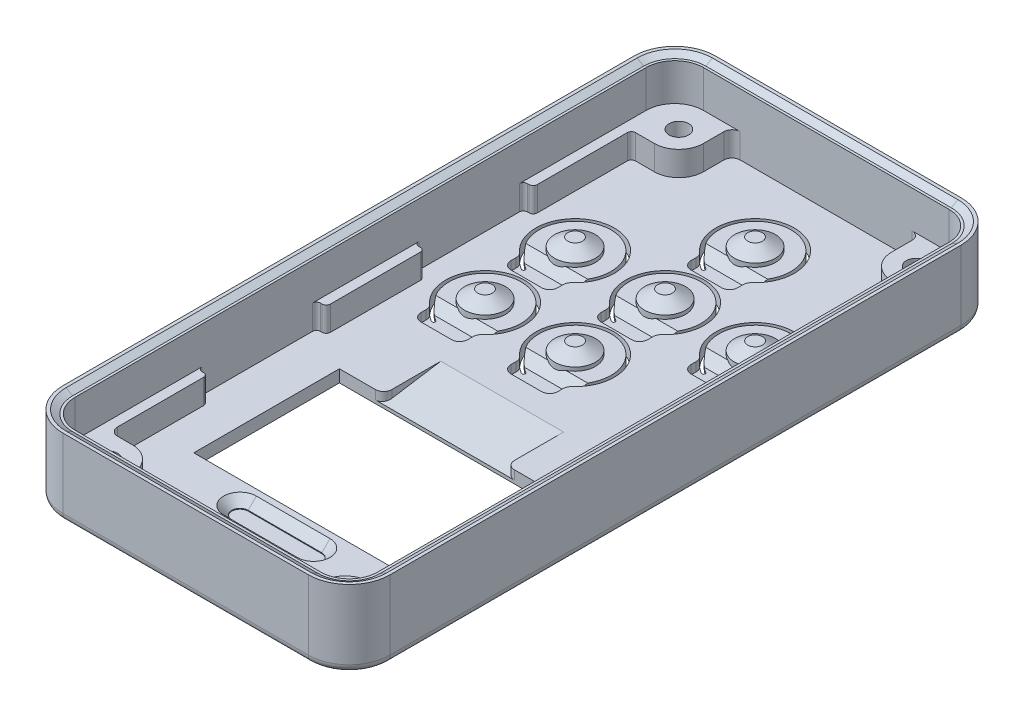
SolidWorks part; units mm, degrees
ref_plane "Front Plane" through (0, 0, 0) normal (0, 0, 1) x (1, 0, 0)
ref_plane "Top Plane" through (0, 0, 0) normal (0, 1, 0) x (1, 0, 0)
ref_plane "Right Plane" through (0, 0, 0) normal (1, 0, 0) x (0, 0, -1)
sketch "Base Sketch" plane through (0, 0, 0) normal (0, 1, 0) x (1, 0, 0)
  line L0 (0, 0) -> (40, 0)
  line L1 (40, 0) -> (40, 79.79)
  line L2 (40, 79.79) -> (0, 79.79)
  line L3 (0, 79.79) -> (0, 0)
extrude "Base" add sketch "Base Sketch" along normal blind 9.5
fillet "Corner Rounds R5" radius 5 4 edges at (0, 4.75, -79.79) (40, 4.75, -79.79) (40, 4.75, 0) (0, 4.75, 0)
shell "Shell 1.5" thickness 1.5 removed face at (20, 9.5, -39.895)
sketch "Boss Sketch" plane through (0, 0, 0) normal (0, 1, 0) x (1, 0, 0)
  line L0 (1.5, 1.5) -> (8.5, 1.5)
  line L1 (8.5, 1.5) -> (8.5, 5)
  line L2 (5.5, 8) -> (1.5, 8)
  line L3 (1.5, 8) -> (1.5, 1.5)
  line L4 (38.5, 1.5) -> (31.5, 1.5)
  line L5 (31.5, 1.5) -> (31.5, 5)
  line L6 (34.5, 8) -> (38.5, 8)
  line L7 (38.5, 8) -> (38.5, 1.5)
  line L16 (1.5, 78.29) -> (8.5, 78.29)
  line L17 (8.5, 78.29) -> (8.5, 74.79)
  line L18 (5.5, 71.79) -> (1.5, 71.79)
  line L19 (1.5, 71.79) -> (1.5, 78.29)
  line L20 (38.5, 78.29) -> (31.5, 78.29)
  line L21 (31.5, 78.29) -> (31.5, 74.79)
  line L22 (34.5, 71.79) -> (38.5, 71.79)
  line L23 (38.5, 71.79) -> (38.5, 78.29)
  arc A0 (8.5, 5) -> (5.5, 8) centre (5.4999, 4.9999) ccw
  circle A1 centre (5.5, 5) radius 1
  arc A2 (31.5, 5) -> (34.5, 8) centre (34.5001, 4.9999) cw
  circle A3 centre (34.5, 5) radius 1
  circle A5 centre (5.5, 74.79) radius 1
  circle A7 centre (34.5, 74.79) radius 1
  arc A8 (8.5, 74.79) -> (5.5, 71.79) centre (5.4999, 74.7901) cw
  arc A9 (31.5, 74.79) -> (34.5, 71.79) centre (34.5001, 74.7901) ccw
extrude "Corner Bosses (stop at ledge y4.5) + M2 Holes" add sketch "Boss Sketch" along normal blind 4.5
sketch "Ledge Sketch" plane through (0, 0, 0) normal (0, 1, 0) x (1, 0, 0)
  line L0 (1.5, 8) -> (2.7, 8)
  line L1 (2.7, 8) -> (2.7, 20)
  line L2 (2.7, 20) -> (1.5, 20)
  line L3 (1.5, 20) -> (1.5, 8)
  line L4 (37.3, 8) -> (38.5, 8)
  line L5 (38.5, 8) -> (38.5, 20)
  line L6 (38.5, 20) -> (37.3, 20)
  line L7 (37.3, 20) -> (37.3, 8)
  line L8 (1.5, 34.5) -> (2.7, 34.5)
  line L9 (2.7, 34.5) -> (2.7, 46.5)
  line L10 (2.7, 46.5) -> (1.5, 46.5)
  line L11 (1.5, 46.5) -> (1.5, 34.5)
  line L12 (37.3, 34.5) -> (38.5, 34.5)
  line L13 (38.5, 34.5) -> (38.5, 46.5)
  line L14 (38.5, 46.5) -> (37.3, 46.5)
  line L15 (37.3, 46.5) -> (37.3, 34.5)
  line L16 (1.5, 59.79) -> (2.7, 59.79)
  line L17 (2.7, 59.79) -> (2.7, 71.79)
  line L18 (2.7, 71.79) -> (1.5, 71.79)
  line L19 (1.5, 71.79) -> (1.5, 59.79)
  line L20 (37.3, 59.79) -> (38.5, 59.79)
  line L21 (38.5, 59.79) -> (38.5, 71.79)
  line L22 (38.5, 71.79) -> (37.3, 71.79)
  line L23 (37.3, 71.79) -> (37.3, 59.79)
extrude "Side Ledges" add sketch "Ledge Sketch" along normal blind 4.5
fillet "Outer Face Round R1" radius 1 8 edges at (1.4645, 0, -1.4645) (20, 0, 0) (38.5355, 0, -1.4645) (40, 0, -39.895) (38.5355, 0, -78.3255) (20, 0, -79.79) (1.4645, 0, -78.3255) (0, 0, -39.895)
sketch "Window Sketch" plane through (0, 0, 0) normal (0, 1, 0) x (1, 0, 0)
  line L0 (7.1, 14.5) -> (32.9, 14.5)
  line L1 (32.9, 14.5) -> (32.9, 31.7)
  line L2 (32.9, 31.7) -> (7.1, 31.7)
  line L3 (7.1, 31.7) -> (7.1, 14.5)
extrude "Display Window" cut sketch "Window Sketch" along normal through all
ref_plane "Mid Plane X20" through (20, 0, 0) normal (1, 0, 0) x (0, 0, -1)
sketch "Ramp Sketch" plane through (20, 0, 0) normal (1, 0, 0) x (0, 0, -1)
  line L0 (31, 0.4) -> (31.7, 0.4)
  line L1 (31.7, 0.4) -> (38.7, 1.5)
  line L2 (38.7, 1.5) -> (38.7, 2.5)
  line L3 (38.7, 2.5) -> (31, 2.5)
  line L4 (31, 2.5) -> (31, 0.4)
extrude "Cable Ramp" cut sketch "Ramp Sketch" against normal blind 7.5 and the other way blind 7.5
ref_plane "Plate Inner Face" through (0, 1.5, 0) normal (0, 1, 0) x (1, 0, 0)
sketch "LED Window Sketch" plane through (0, 1.5, 0) normal (0, 1, 0) x (1, 0, 0)
  circle A0 centre (20, 7.28) radius 1.7
  dimension "D1" = 3.4
extrude "LED Window" cut sketch "LED Window Sketch" against normal blind 1.1
sketch "Plunger Stems Sketch" plane through (0, 1.5, 0) normal (0, 1, 0) x (1, 0, 0)
  circle A0 centre (9, 47.6) radius 2.5
  circle A1 centre (20, 47.6) radius 2.5
  circle A2 centre (9, 58.6) radius 2.5
  circle A3 centre (20, 58.6) radius 2.5
  circle A4 centre (31, 58.6) radius 2.5
  circle A5 centre (20, 69.6) radius 2.5
extrude "Plunger Stems 5.0" add sketch "Plunger Stems Sketch" along normal blind 0.45
ref_plane "Plunger Cone Base" through (0, 1.95, 0) normal (0, 1, 0) x (1, 0, 0)
sketch "Plunger Cone Sketch" plane through (0, 1.95, 0) normal (0, 1, 0) x (1, 0, 0)
  circle A0 centre (9, 47.6) radius 2.5
  circle A1 centre (20, 47.6) radius 2.5
  circle A2 centre (9, 58.6) radius 2.5
  circle A3 centre (20, 58.6) radius 2.5
  circle A4 centre (31, 58.6) radius 2.5
  circle A5 centre (20, 69.6) radius 2.5
extrude "Plunger Cones to 1.8" add sketch "Plunger Cone Sketch" along normal blind 1 draft 57.995
fillet "Boss Junction Fillets R1" radius 1 7 edges at (37.3, 3, -71.79) (37.3, 3, -8) (2.7, 3, -8) (31.5, 3, -78.29) (8.5, 3, -78.29) (31.5, 3, -1.5) (8.5, 3, -1.5)
sketch "C-Slot Sketch" plane through (0, 0, 0) normal (0, 1, 0) x (1, 0, 0)
  arc A0 (10.4434, 43.0222) -> (7.5566, 43.0222) centre (9, 47.6) ccw
  arc A1 (7.5566, 43.0222) -> (7.6769, 43.4036) centre (7.6168, 43.2129) ccw
  arc A2 (7.6769, 43.4036) -> (10.3231, 43.4036) centre (9, 47.6) cw
  arc A3 (10.3231, 43.4036) -> (10.4434, 43.0222) centre (10.3832, 43.2129) ccw
  arc A4 (21.4434, 43.0222) -> (18.5566, 43.0222) centre (20, 47.6) ccw
  arc A5 (18.5566, 43.0222) -> (18.6769, 43.4036) centre (18.6168, 43.2129) ccw
  arc A6 (18.6769, 43.4036) -> (21.3231, 43.4036) centre (20, 47.6) cw
  arc A7 (21.3231, 43.4036) -> (21.4434, 43.0222) centre (21.3832, 43.2129) ccw
  arc A8 (10.4434, 54.0222) -> (7.5566, 54.0222) centre (9, 58.6) ccw
  arc A9 (7.5566, 54.0222) -> (7.6769, 54.4036) centre (7.6168, 54.2129) ccw
  arc A10 (7.6769, 54.4036) -> (10.3231, 54.4036) centre (9, 58.6) cw
  arc A11 (10.3231, 54.4036) -> (10.4434, 54.0222) centre (10.3832, 54.2129) ccw
  arc A12 (21.4434, 54.0222) -> (18.5566, 54.0222) centre (20, 58.6) ccw
  arc A13 (18.5566, 54.0222) -> (18.6769, 54.4036) centre (18.6168, 54.2129) ccw
  arc A14 (18.6769, 54.4036) -> (21.3231, 54.4036) centre (20, 58.6) cw
  arc A15 (21.3231, 54.4036) -> (21.4434, 54.0222) centre (21.3832, 54.2129) ccw
  arc A16 (32.4434, 54.0222) -> (29.5566, 54.0222) centre (31, 58.6) ccw
  arc A17 (29.5566, 54.0222) -> (29.6769, 54.4036) centre (29.6168, 54.2129) ccw
  arc A18 (29.6769, 54.4036) -> (32.3231, 54.4036) centre (31, 58.6) cw
  arc A19 (32.3231, 54.4036) -> (32.4434, 54.0222) centre (32.3832, 54.2129) ccw
  arc A20 (21.4434, 65.0222) -> (18.5566, 65.0222) centre (20, 69.6) ccw
  arc A21 (18.5566, 65.0222) -> (18.6769, 65.4036) centre (18.6168, 65.2129) ccw
  arc A22 (18.6769, 65.4036) -> (21.3231, 65.4036) centre (20, 69.6) cw
  arc A23 (21.3231, 65.4036) -> (21.4434, 65.0222) centre (21.3832, 65.2129) ccw
sketch "Sketch10" plane through (0, 1.5, 0) normal (0, 1, 0) x (1, 0, 0)
  line L0 (11.864, 44.259) -> (11.864, 41.636)
  line L1 (11.864, 41.636) -> (6.136, 41.636)
  line L2 (6.136, 41.636) -> (6.136, 44.259)
  line L3 (6.136, 44.259) -> (11.864, 44.259)
  line L4 (22.864, 44.259) -> (22.864, 41.636)
  line L5 (22.864, 41.636) -> (17.136, 41.636)
  line L6 (17.136, 41.636) -> (17.136, 44.259)
  line L7 (17.136, 44.259) -> (22.864, 44.259)
  line L8 (11.864, 55.259) -> (11.864, 52.636)
  line L9 (11.864, 52.636) -> (6.136, 52.636)
  line L10 (6.136, 52.636) -> (6.136, 55.259)
  line L11 (6.136, 55.259) -> (11.864, 55.259)
  line L12 (22.864, 55.259) -> (22.864, 52.636)
  line L13 (22.864, 52.636) -> (17.136, 52.636)
  line L14 (17.136, 52.636) -> (17.136, 55.259)
  line L15 (17.136, 55.259) -> (22.864, 55.259)
  line L16 (33.864, 55.259) -> (33.864, 52.636)
  line L17 (33.864, 52.636) -> (28.136, 52.636)
  line L18 (28.136, 52.636) -> (28.136, 55.259)
  line L19 (28.136, 55.259) -> (33.864, 55.259)
  line L20 (22.864, 66.259) -> (22.864, 63.636)
  line L21 (22.864, 63.636) -> (17.136, 63.636)
  line L22 (17.136, 63.636) -> (17.136, 66.259)
  line L23 (17.136, 66.259) -> (22.864, 66.259)
extrude "Cut-Extrude7" cut sketch "Sketch10" against normal blind 1.1
sketch "Sketch11" plane through (0, 0, 0) normal (0, 1, 0) x (1, 0, 0)
  arc A0 (11.4, 43.4431) -> (6.6, 43.4431) centre (9, 47.6) ccw
  arc A1 (6.6, 43.4431) -> (6.8, 43.7895) centre (6.7, 43.6163) ccw
  arc A2 (6.8, 43.7895) -> (11.2, 43.7895) centre (9, 47.6) cw
  arc A3 (11.2, 43.7895) -> (11.4, 43.4431) centre (11.3, 43.6163) ccw
  arc A4 (22.4, 43.4431) -> (17.6, 43.4431) centre (20, 47.6) ccw
  arc A5 (17.6, 43.4431) -> (17.8, 43.7895) centre (17.7, 43.6163) ccw
  arc A6 (17.8, 43.7895) -> (22.2, 43.7895) centre (20, 47.6) cw
  arc A7 (22.2, 43.7895) -> (22.4, 43.4431) centre (22.3, 43.6163) ccw
  arc A8 (11.4, 54.4431) -> (6.6, 54.4431) centre (9, 58.6) ccw
  arc A9 (6.6, 54.4431) -> (6.8, 54.7895) centre (6.7, 54.6163) ccw
  arc A10 (6.8, 54.7895) -> (11.2, 54.7895) centre (9, 58.6) cw
  arc A11 (11.2, 54.7895) -> (11.4, 54.4431) centre (11.3, 54.6163) ccw
  arc A12 (22.4, 54.4431) -> (17.6, 54.4431) centre (20, 58.6) ccw
  arc A13 (17.6, 54.4431) -> (17.8, 54.7895) centre (17.7, 54.6163) ccw
  arc A14 (17.8, 54.7895) -> (22.2, 54.7895) centre (20, 58.6) cw
  arc A15 (22.2, 54.7895) -> (22.4, 54.4431) centre (22.3, 54.6163) ccw
  arc A16 (33.4, 54.4431) -> (28.6, 54.4431) centre (31, 58.6) ccw
  arc A17 (28.6, 54.4431) -> (28.8, 54.7895) centre (28.7, 54.6163) ccw
  arc A18 (28.8, 54.7895) -> (33.2, 54.7895) centre (31, 58.6) cw
  arc A19 (33.2, 54.7895) -> (33.4, 54.4431) centre (33.3, 54.6163) ccw
  arc A20 (22.4, 65.4431) -> (17.6, 65.4431) centre (20, 69.6) ccw
  arc A21 (17.6, 65.4431) -> (17.8, 65.7895) centre (17.7, 65.6163) ccw
  arc A22 (17.8, 65.7895) -> (22.2, 65.7895) centre (20, 69.6) cw
  arc A23 (22.2, 65.7895) -> (22.4, 65.4431) centre (22.3, 65.6163) ccw
extrude "Button C-Slots 300deg 0.4" cut sketch "Sketch11" along normal through all
chamfer "Chamfer1" distance 1.1 angle 45 6 edges at (9, 1.5, -44.259) (20, 1.5, -66.259) (31, 1.5, -55.259) (20, 1.5, -55.259) (9, 1.5, -55.259) (20, 1.5, -44.259)
fillet "Fillet1" radius 1 24 edges at (11.864, 0.95, -43.7481) (11.864, 0.95, -41.636) (6.136, 0.95, -41.636) (6.136, 0.95, -43.7481) (22.864, 0.95, -63.636) (22.864, 0.95, -65.7481) (17.136, 0.95, -63.636) (17.136, 0.95, -65.7481) (33.864, 0.95, -52.636) (33.864, 0.95, -54.7481) (28.136, 0.95, -52.636) (28.136, 0.95, -54.7481) (22.864, 0.95, -52.636) (22.864, 0.95, -54.7481) (17.136, 0.95, -52.636) (17.136, 0.95, -54.7481) (11.864, 0.95, -52.636) (11.864, 0.95, -54.7481) (6.136, 0.95, -52.636) (6.136, 0.95, -54.7481) (22.864, 0.95, -41.636) (22.864, 0.95, -43.7481) (17.136, 0.95, -41.636) (17.136, 0.95, -43.7481)
fillet "Fillet2" radius 0.5 17 edges at (2.7, 3, -71.79) (1.5, 3, -59.79) (2.7, 3, -59.79) (38.5, 3, -59.79) (37.3, 3, -59.79) (38.5, 3, -46.5) (37.3, 3, -46.5) (2.7, 3, -46.5) (1.5, 3, -46.5) (38.5, 3, -34.5) (37.3, 3, -34.5) (2.7, 3, -34.5) (1.5, 3, -34.5) (38.5, 3, -20) (37.3, 3, -20) (2.7, 3, -20) (1.5, 3, -20)
fillet "Fillet3" radius 1 2 edges at (27.5, 0.95, -31.7) (12.5, 0.95, -31.7)
sketch "Button Symbols Cut Sketch" plane through (0, 0, 0) normal (0, 1, 0) x (1, 0, 0)
  line L0 (7.0908, 45.6908) -> (7.7272, 46.3272)
  line L1 (10.2728, 46.3272) -> (10.9092, 45.6908)
  line L2 (8.55, 47.2) -> (9.45, 47.2)
  line L3 (9.45, 47.2) -> (9.45, 44.4)
  line L4 (9.45, 44.4) -> (8.55, 44.4)
  line L5 (8.55, 44.4) -> (8.55, 47.2)
  line L6 (20, 44.8) -> (22.4249, 49)
  line L7 (22.4249, 49) -> (17.5751, 49)
  line L8 (17.5751, 49) -> (20, 44.8)
  line L9 (6.2, 58.6) -> (10.4, 56.1751)
  line L10 (10.4, 56.1751) -> (10.4, 61.0249)
  line L11 (10.4, 61.0249) -> (6.2, 58.6)
  line L12 (33.8, 58.6) -> (29.6, 61.0249)
  line L13 (29.6, 61.0249) -> (29.6, 56.1751)
  line L14 (29.6, 56.1751) -> (33.8, 58.6)
  line L15 (20, 72.4) -> (17.5751, 68.2)
  line L16 (17.5751, 68.2) -> (22.4249, 68.2)
  line L17 (22.4249, 68.2) -> (20, 72.4)
  arc A0 (10.9092, 45.6908) -> (7.0908, 45.6908) centre (9, 47.6) ccw
  arc A1 (7.7272, 46.3272) -> (10.2728, 46.3272) centre (9, 47.6) cw
  circle A2 centre (20, 58.6) radius 2.4
  circle A3 centre (20, 58.6) radius 1.5
sketch "Button Symbols Inlay Sketch" plane through (0, 0, 0) normal (0, 1, 0) x (1, 0, 0)
  line L0 (7.0908, 45.6908) -> (7.7272, 46.3272)
  line L1 (10.2728, 46.3272) -> (10.9092, 45.6908)
  line L2 (8.55, 47.2) -> (9.45, 47.2)
  line L3 (9.45, 47.2) -> (9.45, 44.4)
  line L4 (9.45, 44.4) -> (8.55, 44.4)
  line L5 (8.55, 44.4) -> (8.55, 47.2)
  line L6 (20, 44.8) -> (22.4249, 49)
  line L7 (22.4249, 49) -> (17.5751, 49)
  line L8 (17.5751, 49) -> (20, 44.8)
  line L9 (6.2, 58.6) -> (10.4, 56.1751)
  line L10 (10.4, 56.1751) -> (10.4, 61.0249)
  line L11 (10.4, 61.0249) -> (6.2, 58.6)
  line L12 (33.8, 58.6) -> (29.6, 61.0249)
  line L13 (29.6, 61.0249) -> (29.6, 56.1751)
  line L14 (29.6, 56.1751) -> (33.8, 58.6)
  line L15 (20, 72.4) -> (17.5751, 68.2)
  line L16 (17.5751, 68.2) -> (22.4249, 68.2)
  line L17 (22.4249, 68.2) -> (20, 72.4)
  arc A0 (10.9092, 45.6908) -> (7.0908, 45.6908) centre (9, 47.6) ccw
  arc A1 (7.7272, 46.3272) -> (10.2728, 46.3272) centre (9, 47.6) cw
  circle A2 centre (20, 58.6) radius 2.4
  circle A3 centre (20, 58.6) radius 1.5
sketch "Sketch14" plane through (0, 0, 0) normal (0, 1, 0) x (1, 0, 0)
  line L0 (8.4, 47) -> (8.4, 45.2)
  line L1 (9.6, 45.2) -> (9.6, 47)
  line L2 (20.5196, 44.9) -> (22.7713, 48.8)
  line L3 (22.2517, 49.7) -> (17.7483, 49.7)
  line L4 (17.2287, 48.8) -> (19.4804, 44.9)
  line L5 (6.1, 58.0804) -> (10, 55.8287)
  line L6 (10.9, 56.3483) -> (10.9, 60.8517)
  line L7 (10, 61.3713) -> (6.1, 59.1196)
  line L8 (33.9, 59.1196) -> (30, 61.3713)
  line L9 (29.1, 60.8517) -> (29.1, 56.3483)
  line L10 (30, 55.8287) -> (33.9, 58.0804)
  line L11 (19.4804, 72.5) -> (17.2287, 68.6)
  line L12 (17.7483, 67.7) -> (22.2517, 67.7)
  line L13 (22.7713, 68.6) -> (20.5196, 72.5)
  arc A0 (11.4513, 45.5431) -> (6.5487, 45.5431) centre (9, 47.6) ccw
  arc A1 (6.5487, 45.5431) -> (7.4679, 46.3144) centre (7.0083, 45.9288) ccw
  arc A2 (7.4679, 46.3144) -> (10.5321, 46.3144) centre (9, 47.6) cw
  arc A3 (10.5321, 46.3144) -> (11.4513, 45.5431) centre (10.9917, 45.9288) ccw
  arc A4 (8.4, 45.2) -> (9.6, 45.2) centre (9, 45.2) ccw
  arc A5 (9.6, 47) -> (8.4, 47) centre (9, 47) ccw
  arc A6 (19.4804, 44.9) -> (20.5196, 44.9) centre (20, 45.2) ccw
  arc A7 (22.7713, 48.8) -> (22.2517, 49.7) centre (22.2517, 49.1) ccw
  arc A8 (17.7483, 49.7) -> (17.2287, 48.8) centre (17.7483, 49.1) ccw
  arc A9 (6.1, 59.1196) -> (6.1, 58.0804) centre (6.4, 58.6) ccw
  arc A10 (10, 55.8287) -> (10.9, 56.3483) centre (10.3, 56.3483) ccw
  arc A11 (10.9, 60.8517) -> (10, 61.3713) centre (10.3, 60.8517) ccw
  circle A12 centre (20, 58.6) radius 3.1
  circle A13 centre (20, 58.6) radius 1.9
  arc A14 (33.9, 58.0804) -> (33.9, 59.1196) centre (33.6, 58.6) ccw
  arc A15 (30, 61.3713) -> (29.1, 60.8517) centre (29.7, 60.8517) ccw
  arc A16 (29.1, 56.3483) -> (30, 55.8287) centre (29.7, 56.3483) ccw
  arc A17 (20.5196, 72.5) -> (19.4804, 72.5) centre (20, 72.2) ccw
  arc A18 (17.2287, 68.6) -> (17.7483, 67.7) centre (17.7483, 68.3) ccw
  arc A19 (22.2517, 67.7) -> (22.7713, 68.6) centre (22.2517, 68.3) ccw
extrude "Button Symbol Recess 0.4" cut sketch "Sketch14" along normal blind 0.4
sketch "Sketch15" plane through (0, 0, 0) normal (0, 1, 0) x (1, 0, 0)
  line L0 (8.4, 47) -> (8.4, 45.2)
  line L1 (9.6, 45.2) -> (9.6, 47)
  line L2 (20.5196, 44.9) -> (22.7713, 48.8)
  line L3 (22.2517, 49.7) -> (17.7483, 49.7)
  line L4 (17.2287, 48.8) -> (19.4804, 44.9)
  line L5 (6.1, 58.0804) -> (10, 55.8287)
  line L6 (10.9, 56.3483) -> (10.9, 60.8517)
  line L7 (10, 61.3713) -> (6.1, 59.1196)
  line L8 (33.9, 59.1196) -> (30, 61.3713)
  line L9 (29.1, 60.8517) -> (29.1, 56.3483)
  line L10 (30, 55.8287) -> (33.9, 58.0804)
  line L11 (19.4804, 72.5) -> (17.2287, 68.6)
  line L12 (17.7483, 67.7) -> (22.2517, 67.7)
  line L13 (22.7713, 68.6) -> (20.5196, 72.5)
  arc A0 (11.4513, 45.5431) -> (6.5487, 45.5431) centre (9, 47.6) ccw
  arc A1 (6.5487, 45.5431) -> (7.4679, 46.3144) centre (7.0083, 45.9288) ccw
  arc A2 (7.4679, 46.3144) -> (10.5321, 46.3144) centre (9, 47.6) cw
  arc A3 (10.5321, 46.3144) -> (11.4513, 45.5431) centre (10.9917, 45.9288) ccw
  arc A4 (8.4, 45.2) -> (9.6, 45.2) centre (9, 45.2) ccw
  arc A5 (9.6, 47) -> (8.4, 47) centre (9, 47) ccw
  arc A6 (19.4804, 44.9) -> (20.5196, 44.9) centre (20, 45.2) ccw
  arc A7 (22.7713, 48.8) -> (22.2517, 49.7) centre (22.2517, 49.1) ccw
  arc A8 (17.7483, 49.7) -> (17.2287, 48.8) centre (17.7483, 49.1) ccw
  arc A9 (6.1, 59.1196) -> (6.1, 58.0804) centre (6.4, 58.6) ccw
  arc A10 (10, 55.8287) -> (10.9, 56.3483) centre (10.3, 56.3483) ccw
  arc A11 (10.9, 60.8517) -> (10, 61.3713) centre (10.3, 60.8517) ccw
  circle A12 centre (20, 58.6) radius 3.1
  circle A13 centre (20, 58.6) radius 1.9
  arc A14 (33.9, 58.0804) -> (33.9, 59.1196) centre (33.6, 58.6) ccw
  arc A15 (30, 61.3713) -> (29.1, 60.8517) centre (29.7, 60.8517) ccw
  arc A16 (29.1, 56.3483) -> (30, 55.8287) centre (29.7, 56.3483) ccw
  arc A17 (20.5196, 72.5) -> (19.4804, 72.5) centre (20, 72.2) ccw
  arc A18 (17.2287, 68.6) -> (17.7483, 67.7) centre (17.7483, 68.3) ccw
  arc A19 (22.2517, 67.7) -> (22.7713, 68.6) centre (22.2517, 68.3) ccw
extrude "Button Symbol Inlays 0.4 (colour 2)" add sketch "Sketch15" along normal blind 0.4 separate body
sketch "I2C Header Pocket Sketch" plane through (0, 1.5, 0) normal (0, 1, 0) x (1, 0, 0)
  line L0 (15.5, 9.4) -> (24.5, 9.4)
  line L1 (25.5, 10.4) -> (25.5, 11.9)
  line L2 (24.5, 12.9) -> (15.5, 12.9)
  line L3 (14.5, 11.9) -> (14.5, 10.4)
  line L4 (32.9, 14.5) -> (7.1, 14.5) construction
  arc A0 (24.5, 9.4) -> (25.5, 10.4) centre (24.5, 10.4) ccw
  arc A1 (25.5, 11.9) -> (24.5, 12.9) centre (24.5, 11.9) ccw
  arc A2 (15.5, 12.9) -> (14.5, 11.9) centre (15.5, 11.9) ccw
  arc A3 (14.5, 10.4) -> (15.5, 9.4) centre (15.5, 10.4) ccw
  dimension "D3" = 1
  dimension "D1" = 1.6
  dimension "D2" = 11
  dimension "D4" = 2.6
sketch "Sketch17" plane through (0, 1.5, 0) normal (0, 1, 0) x (1, 0, 0)
  line L0 (15.2, 10.45) -> (24.8, 10.45)
  line L1 (24.8, 11.85) -> (15.2, 11.85)
  arc A0 (24.8, 10.45) -> (24.8, 11.85) centre (24.8, 11.15) ccw
  arc A1 (15.2, 11.85) -> (15.2, 10.45) centre (15.2, 11.15) ccw
sketch "Sketch18" plane through (0, 0, -14.5) normal (0, 0, -1) x (-1, 0, 0)
  line L4 (-32.9, 1.5) -> (-32.9, 0)
  line L5 (-32.9, 0) -> (-7.1, 0)
  line L6 (-7.1, 0) -> (-7.1, 1.5)
  line L7 (-7.1, 1.5) -> (-32.9, 1.5)
  line L8 (-32.9, 1.5) -> (-32.9, 0)
  line L9 (-32.9, 0) -> (-7.1, 0)
  line L10 (-7.1, 0) -> (-7.1, 1.5)
  line L11 (-7.1, 1.5) -> (-32.9, 1.5)
  dimension "D1" = 0
extrude "Cut-Extrude16" cut sketch "Sketch18" against normal blind 0.6
sketch "Sketch19" plane through (0, 1.5, 0) normal (0, 1, 0) x (1, 0, 0)
  line L0 (15.2999, 10.35) -> (24.7001, 10.35)
  line L1 (25.5, 11.1499) -> (25.5, 11.1501)
  line L2 (24.7001, 11.95) -> (15.2999, 11.95)
  line L3 (14.5, 11.1501) -> (14.5, 11.1499)
  arc A0 (24.7001, 10.35) -> (25.5, 11.1499) centre (24.7001, 11.1499) ccw
  arc A1 (25.5, 11.1501) -> (24.7001, 11.95) centre (24.7001, 11.1501) ccw
  arc A2 (15.2999, 11.95) -> (14.5, 11.1501) centre (15.2999, 11.1501) ccw
  arc A3 (14.5, 11.1499) -> (15.2999, 10.35) centre (15.2999, 11.1499) ccw
sketch "Sketch20" plane through (0, 1.5, 0) normal (0, 1, 0) x (1, 0, 0)
  line L0 (15.5, 10.15) -> (24.5, 10.15)
  line L1 (24.5, 12.15) -> (15.5, 12.15)
  arc A0 (24.5, 10.15) -> (24.5, 12.15) centre (24.5, 11.15) ccw
  arc A1 (15.5, 12.15) -> (15.5, 10.15) centre (15.5, 11.15) ccw
extrude "I2C Header Lead Pocket 2.0 (0.2 skin)" cut sketch "Sketch20" against normal blind 1.1
chamfer "Chamfer3" distance 1 angle 45 4 edges at (20, 1.5, -12.15) (14.5, 1.5, -11.15) (25.5, 1.5, -11.15) (20, 1.5, -10.15)
sketch "Sketch21" plane through (0, 0, 0) normal (0, -1, 0) x (1, 0, 0)
  circle A0 centre (20, -7.28) radius 2.5
  circle A1 centre (20, -7.28) radius 1.7
  circle A2 centre (20, -7.28) radius 1.7 construction
  circle A3 centre (20, -7.28) radius 2.6
  dimension "D2" = 5
  dimension "D3" = 0.1
  dimension "D1" = 0
extrude "Cut-Extrude17" cut sketch "Sketch21" against normal blind 0.1
sketch "M2 Clearance 2.4 (screw from front) Sketch" plane through (0, 0, 0) normal (0, 1, 0) x (1, 0, 0)
  circle A0 centre (5.5, 5) radius 1.2
  circle A1 centre (34.5, 5) radius 1.2
  circle A2 centre (5.5, 74.79) radius 1.2
  circle A3 centre (34.5, 74.79) radius 1.2
extrude "M2 Clearance 2.4 (screw from front)" cut sketch "M2 Clearance 2.4 (screw from front) Sketch" along normal through all
sketch "M2 Head Counterbore 4.4 x 2.0 Sketch" plane through (0, 0, 0) normal (0, 1, 0) x (1, 0, 0)
  circle A0 centre (5.5, 5) radius 2.2
  circle A1 centre (34.5, 5) radius 2.2
  circle A2 centre (5.5, 74.79) radius 2.2
  circle A3 centre (34.5, 74.79) radius 2.2
extrude "M2 Head Counterbore 4.4 x 2.0" cut sketch "M2 Head Counterbore 4.4 x 2.0 Sketch" along normal blind 2
chamfer "M2 CSK Seats (head 1 mm below face)" distance 1 angle 45 4 edges at (34.5, 2, -72.59) (5.5, 2, -72.59) (34.5, 2, -2.8) (5.5, 2, -2.8)
ref_plane "Joint Bevel Plane" through (0, 9.0381, 0) normal (0, 1, 0) x (1, 0, 0)
sketch "Wall Bevel 30deg + 0.4 flats Sketch" plane through (0, 9.0381, 0) normal (0, 1, 0) x (1, 0, 0)
  line L0 (5, 1.2) -> (35, 1.2)
  line L1 (38.8, 5) -> (38.8, 74.79)
  line L2 (35, 78.59) -> (5, 78.59)
  line L3 (1.2, 74.79) -> (1.2, 5)
  arc A0 (35, 1.2) -> (38.8, 5) centre (35, 5) ccw
  arc A1 (38.8, 74.79) -> (35, 78.59) centre (35, 74.79) ccw
  arc A2 (5, 78.59) -> (1.2, 74.79) centre (5, 74.79) ccw
  arc A3 (1.2, 5) -> (5, 1.2) centre (5, 5) ccw
extrude "Wall Bevel 30deg + 0.4 flats" cut sketch "Wall Bevel 30deg + 0.4 flats Sketch" along normal blind 0.4619 draft 60 draft outward yes
